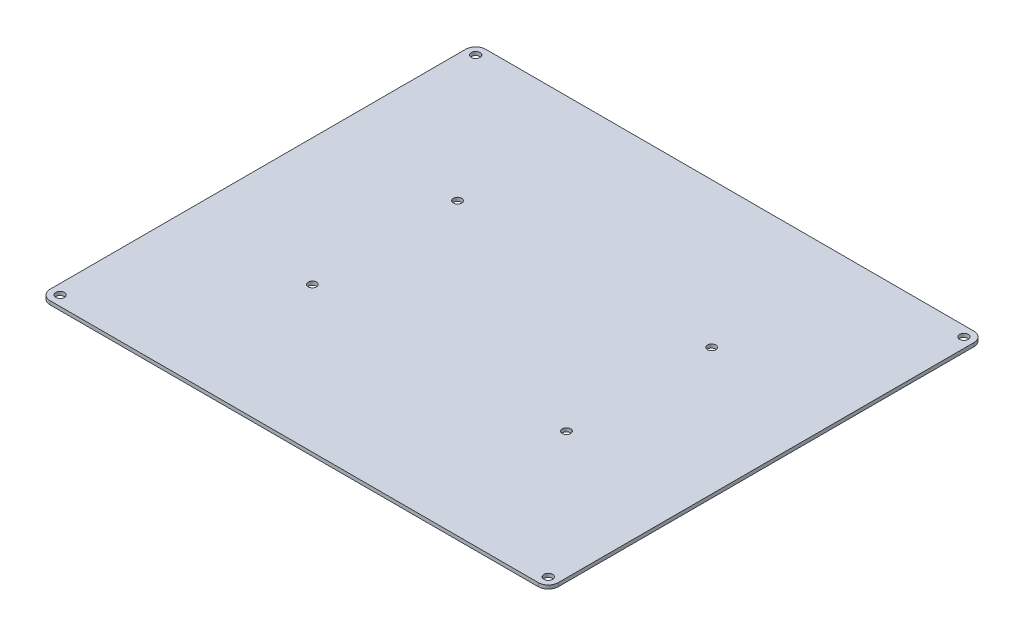
SolidWorks part; units mm, degrees
ref_plane "Front Plane" through (0, 0, 0) normal (0, 0, 1) x (1, 0, 0)
ref_plane "Top Plane" through (0, 0, 0) normal (0, 1, 0) x (1, 0, 0)
ref_plane "Right Plane" through (0, 0, 0) normal (1, 0, 0) x (0, 0, -1)
sketch "Sketch1" plane through (0, 0, 0) normal (0, 1, 0) x (1, 0, 0)
  line L0 (70, 0) -> (70, -120) construction
  line L1 (0, 0) -> (140, 0)
  line L2 (0, 0) -> (0, -120)
  line L3 (0, -120) -> (140, -120)
  line L4 (140, 0) -> (140, -120)
  line L5 (2.75, -2.75) -> (0, -2.75) construction
  line L6 (0, -60) -> (140, -60) construction
  line L7 (105, -40) -> (70, -60) construction
  line L8 (2.75, 0) -> (2.75, -2.75) construction
  line L9 (70, -60) -> (35, -80) construction
  circle A0 centre (2.75, -2.75) radius 1.2
  circle A1 centre (137.25, -2.75) radius 1.2
  circle A2 centre (137.25, -117.25) radius 1.2
  circle A3 centre (2.75, -117.25) radius 1.2
  circle A4 centre (35, -40) radius 1.15
  circle A5 centre (105, -40) radius 1.15
  circle A6 centre (35, -80) radius 1.15
  circle A7 centre (105, -80) radius 1.15
  dimension "D3" = 2.4
  dimension "D4" = 2.75
  dimension "D5" = 2.3
  dimension "D1" = 140
  dimension "D2" = 120
  dimension "D6" = 70
  dimension "D7" = 40
extrude "Boss-Extrude1" add sketch "Sketch1" along normal blind 1
fillet "Fillet1" radius 2.75 4 edges at (0, 0.5, 0) (140, 0.5, 0) (140, 0.5, 120) (0, 0.5, 120)
